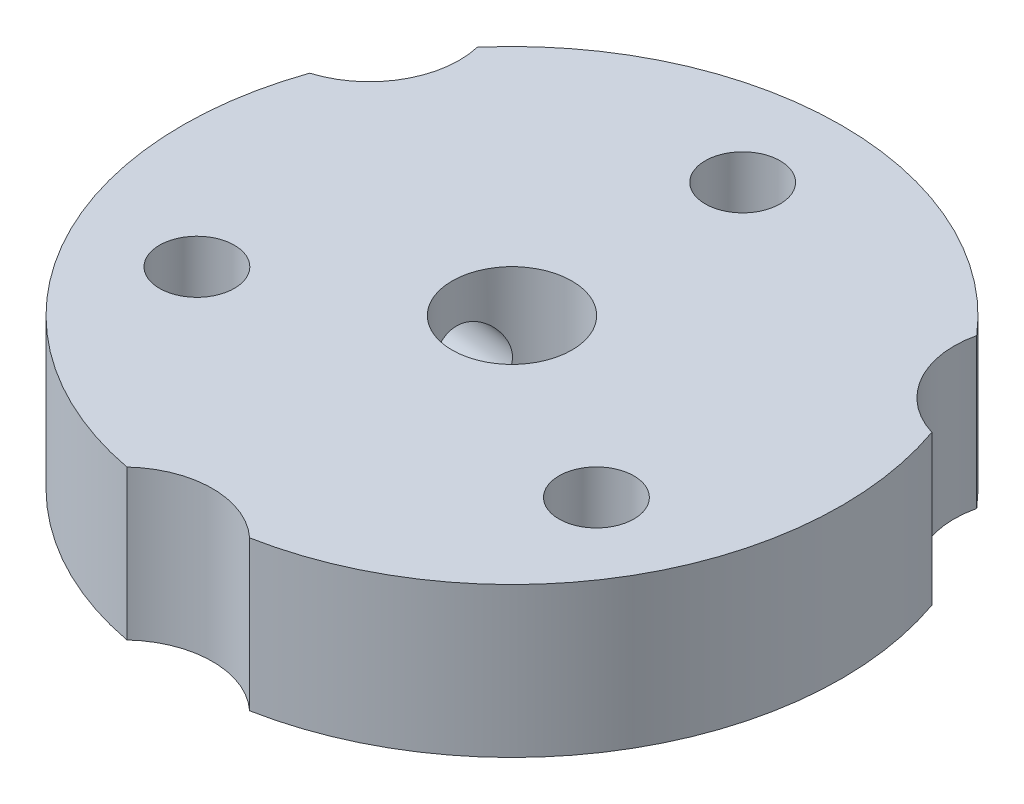
SolidWorks part; units mm, degrees
ref_plane "Plano frontal" through (0, 0, 0) normal (0, 0, 1) x (1, 0, 0)
ref_plane "Plano superior" through (0, 0, 0) normal (0, 1, 0) x (1, 0, 0)
ref_plane "Plano direito" through (0, 0, 0) normal (1, 0, 0) x (0, 0, -1)
sketch "Esboço1" plane through (0, 0, 0) normal (0, 1, 0) x (1, 0, 0)
  circle A0 centre (0, 0) radius 11
  dimension "D1" = 22
extrude "Ressalto-extrusão1" add sketch "Esboço1" along normal blind 5
sketch "Esboço3" plane through (0, 5, 0) normal (0, 1, 0) x (1, 0, 0)
  circle A1 centre (0, 7.7) radius 1.25
  circle A2 centre (6.6684, -3.85) radius 1.25
  circle A3 centre (-6.6684, -3.85) radius 1.25
  dimension "D3" = 2.5
  dimension "D1" = 7.7
  dimension "D2" = 7.7
extrude "Corte-extrusão1" cut sketch "Esboço3" against normal blind 10.096
sketch "Esboço22" plane through (0, 5, 0) normal (0, 1, 0) x (1, 0, 0)
  circle A1 centre (-11.2583, 6.5) radius 3
  circle A2 centre (0, -13) radius 3
  circle A3 centre (11.2583, 6.5) radius 3
  dimension "D1" = 6
extrude "Corte-extrusão6" cut sketch "Esboço22" against normal blind 5.5
sketch "Esboço23" plane through (0, 0, 0) normal (0, -1, 0) x (-1, 0, 0)
  circle A0 centre (-6.6684, -3.85) radius 3
  circle A1 centre (6.6684, -3.85) radius 3
  circle A2 centre (0, 7.7) radius 3
  dimension "D1" = 6
extrude "Corte-extrusão7" cut sketch "Esboço23" against normal blind 1.5
sketch "Esboço27" plane through (0, 0, 0) normal (0, -1, 0) x (1, 0, 0)
  circle A0 centre (0, 0) radius 2
extrude "Corte-extrusão8" cut sketch "Esboço27" against normal blind 10
hole_wizard "Broca de rosquear para tarraxa de M3x0.52" positions "3DSketch2" profile "Esboço28" hole size "M3x0.5" standard "Ansi Metric" end condition up to next
sketch3d "3DSketch2"
  point P0 (-10.9259, 2.3829, -1.2747)
sketch "Esboço28" plane through (-10.9259, 2.3829, -1.2747) normal (0, 1, 0) x (-0.1159, 0, 0.9933)
  line L0 (0, 0) -> (0, 9)
  line L1 (0, 9) -> (1.25, 9)
  line L2 (1.25, 9) -> (1.25, 0.025)
  line L3 (1.25, 0.025) -> (1.275, 0)
  line L5 (1.275, 0) -> (0, 0)
  line L6 (-1.25, 0.025) -> (-1.275, 0) construction
  line L11 (0, -6.35) -> (0, 107.95) construction
  dimension "Thru Hole Dia." = 2.5
  dimension "Thru Hole Depth" = 9
  dimension "Near C'Sink Dia." = 2.55
  dimension "Near C'Sink Angle" = 90
